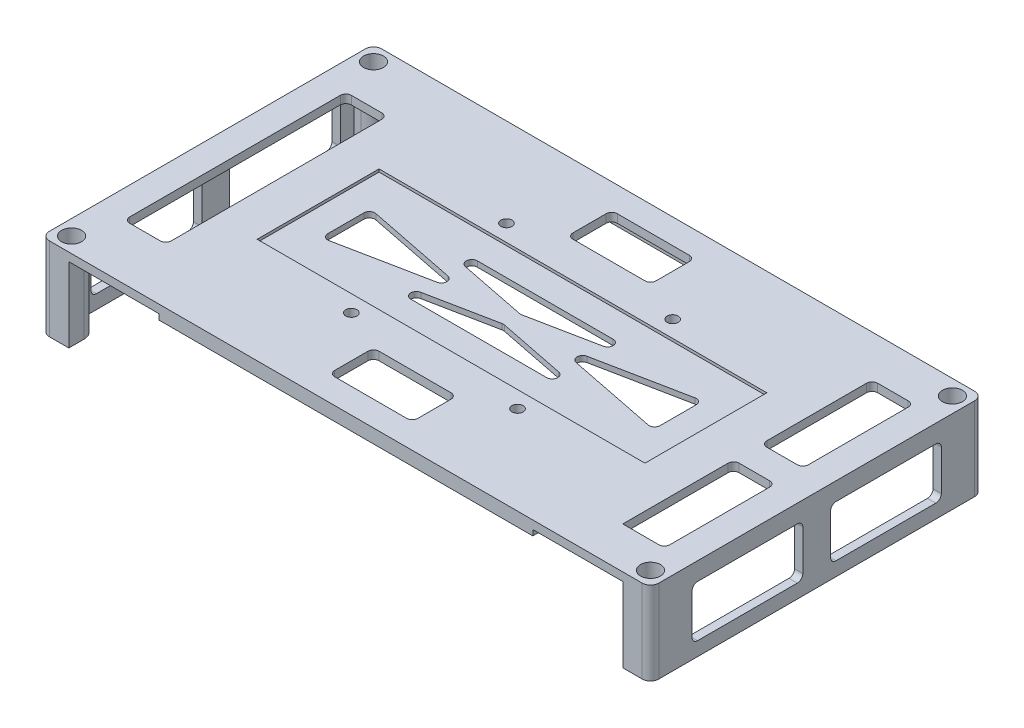
SolidWorks part; units mm, degrees
material "ABS"
ref_plane "前基準面" through (0, 0, 0) normal (0, 0, 1) x (1, 0, 0)
ref_plane "上基準面" through (0, 0, 0) normal (0, 1, 0) x (1, 0, 0)
ref_plane "右基準面" through (0, 0, 0) normal (1, 0, 0) x (0, 0, -1)
sketch "草圖8" plane through (0, 0, 0) normal (0, 1, 0) x (1, 0, 0)
  line L1 (-110, 60) -> (110, 60)
  line L2 (-110, 60) -> (-110, -60)
  line L3 (-110, -60) -> (110, -60)
  line L4 (110, 60) -> (110, -60)
extrude "填料-伸長6" add sketch "草圖8" along normal blind 3
sketch "草圖10" plane through (0, 0, 0) normal (0, -1, 0) x (1, 0, 0)
  line L1 (-110, 60) -> (-100, 60)
  line L2 (-110, 60) -> (-110, -60)
  line L3 (-110, -60) -> (-100, -60)
  line L4 (-100, 60) -> (-100, -60)
  line L5 (0, 0) -> (0, 67.9588) construction
  line L6 (0, 0) -> (59.8785, 0) construction
  line L7 (110, -60) -> (100, -60)
  line L8 (100, 60) -> (100, -60)
  line L9 (110, 60) -> (100, 60)
  line L10 (110, 60) -> (110, -60)
  dimension "D2" = 10
extrude "填料-伸長7" add sketch "草圖10" along normal blind 27
sketch "草圖9" plane through (0, 0, 0) normal (0, 1, 0) x (1, 0, 0)
  line L0 (-1000, 0) -> (49000, 0) construction
  line L1 (0, -994.7968) -> (0, 49005.2032) construction
  line L2 (110, 60) -> (-110, 60) construction
  line L4 (110, -60) -> (110, 60) construction
  circle A0 centre (104.5, 54.5) radius 2.05
  circle A1 centre (-104.5, 54.5) radius 2.05
  circle A2 centre (-104.5, -54.5) radius 2.05
  circle A3 centre (104.5, -54.5) radius 2.05
  circle A6 centre (30, 28) radius 2
  circle A7 centre (-30, 28) radius 2
  circle A8 centre (30, -28) radius 2
  circle A9 centre (-30, -28) radius 2
  dimension "D1" = 4.1
  dimension "D5" = 4
  dimension "D2" = 5.5
  dimension "D3" = 5.5
  dimension "D6" = 30
  dimension "D7" = 28
extrude "除料-伸長1" cut sketch "草圖9" against normal through all and the other way through all contours A1 | A2 | A0 | A3
sketch "草圖11" plane through (0, 3, 0) normal (0, 1, 0) x (1, 0, 0)
  line L0 (0.0013, 21.2615) -> (0.0013, 0) construction
  line L1 (0.0013, 0) -> (-26.9987, 0) construction
  line L2 (110, -60) -> (110, 60) construction
  line L3 (110, 60) -> (-110, 60) construction
  circle A0 centre (-104.4974, 54.5) radius 3.6
  circle A1 centre (-104.4974, -54.5) radius 3.6
  circle A2 centre (104.5, -54.5) radius 3.6
  circle A3 centre (104.5, 54.5) radius 3.6
  dimension "D1" = 7.2
  dimension "D2" = 5.5
  dimension "D4" = 5.5
extrude "除料-伸長2" cut sketch "草圖11" against normal blind 25 contours A1 | A0 | A3 | A2
sketch "草圖13" plane through (0, 0, 0) normal (1, 0, 0) x (0, 0, -1)
  line L0 (0, 0) -> (0, -20.0336) construction
  line L2 (-45, -3.5) -> (-5, -3.5)
  line L3 (-45, -3.5) -> (-45, -22)
  line L4 (-45, -22) -> (-5, -22)
  line L5 (-5, -3.5) -> (-5, -22)
  line L6 (60, -27) -> (-60, -27) construction
  line L8 (45, -3.5) -> (45, -22)
  line L9 (5, -3.5) -> (5, -22)
  line L10 (45, -22) -> (5, -22)
  line L11 (45, -3.5) -> (5, -3.5)
  line L12 (-60, 3) -> (-60, -27) construction
  dimension "D1" = 18.5
  dimension "D2" = 5
  dimension "D3" = 15
  dimension "D4" = 10
extrude "除料-伸長4" cut sketch "草圖13" against normal through all both and the other way through all
sketch "草圖14" plane through (0, 3, 0) normal (0, 1, 0) x (1, 0, 0)
  line L0 (0, 0) -> (-46.215, 0) construction
  line L1 (0, 0) -> (0, 32.6806) construction
  line L3 (-70, -22) -> (70, -22)
  line L4 (-70, -22) -> (-70, 22)
  line L5 (-70, 22) -> (70, 22)
  line L6 (70, -22) -> (70, 22)
  line L7 (-70, -22) -> (70, 22) construction
  line L8 (-70, 22) -> (70, -22) construction
  dimension "D1" = 140
  dimension "D2" = 44
extrude "除料-伸長7" cut sketch "草圖14" against normal blind 1
sketch "草圖15" plane through (0, 3, 0) normal (0, 1, 0) x (1, 0, 0)
  line L0 (0, 0) -> (27.6246, 0) construction
  line L1 (-100, 40) -> (-85, 40)
  line L2 (-100, 40) -> (-100, -40)
  line L3 (-100, -40) -> (-85, -40)
  line L4 (-85, 40) -> (-85, -40)
  line L5 (0, 0) -> (0, 35.214) construction
  line L6 (100, 5) -> (85, 5)
  line L7 (85, 45) -> (85, 5)
  line L8 (100, 45) -> (85, 45)
  line L9 (100, 45) -> (100, 5)
  line L10 (70, 22) -> (-70, 22) construction
  line L11 (-44.7029, -12) -> (44.7029, -12)
  line L12 (-60, -8.9406) -> (-60, 8.9406)
  line L13 (-44.7029, 12) -> (44.7029, 12)
  line L14 (60, -8.9406) -> (60, 8.9406)
  line L15 (-15, -35) -> (15, -35)
  line L16 (0, -3.0594) -> (44.7029, -12)
  line L17 (-70, 22) -> (-70, -22) construction
  line L18 (-60, 8.9406) -> (-15.2971, 0)
  line L19 (-44.7029, -12) -> (0, -3.0594)
  line L20 (-44.7029, 12) -> (0, 3.0594)
  line L21 (-60, -8.9406) -> (-15.2971, 0)
  line L22 (-15, 51) -> (15, 51)
  line L23 (-15, 51) -> (-15, 35)
  line L24 (-15, 35) -> (15, 35)
  line L25 (15, 51) -> (15, 35)
  line L26 (15, -51) -> (15, -35)
  line L27 (-15, -51) -> (15, -51)
  line L28 (15.2971, 0) -> (60, -8.9406)
  line L29 (0, 3.0594) -> (44.7029, 12)
  line L30 (15.2971, 0) -> (60, 8.9406)
  line L31 (-15, -51) -> (-15, -35)
  line L32 (100, -45) -> (100, -5)
  line L33 (100, -45) -> (85, -45)
  line L34 (85, -45) -> (85, -5)
  line L35 (100, -5) -> (85, -5)
  line L36 (110, 60) -> (-110, 60) construction
  dimension "D1" = 40
  dimension "D2" = 85
  dimension "D3" = 15
  dimension "D4" = 10
  dimension "D5" = 10
  dimension "D6" = 30
  dimension "D7" = 16
  dimension "D8" = 35
  dimension "D9" = 85
  dimension "D10" = 80
  dimension "D11" = 15
extrude "除料-伸長8" cut sketch "草圖15" against normal through all
extrude "除料-伸長9" cut sketch "草圖9<5>" along normal through all contours A7 | A6 | A9 | A8
sketch "草圖9<5>" plane through (0, 0, 0) normal (0, 1, 0) x (1, 0, 0) same geometry as "草圖9"
sketch "草圖19" plane through (0, -27, 0) normal (0, -1, 0) x (1, 0, 0)
  line L5 (0, -57.1205) -> (0, 57.1205) construction
  line L6 (0, 0) -> (-76.5655, 0) construction
  line L12 (-100, 54.5) -> (-100, -54.5)
  line L15 (-110, 60) -> (-110, -60) construction
  line L16 (-104.5, 50) -> (-107, 50)
  line L18 (-104.5, -50) -> (-107, -50)
  line L19 (-107, 50) -> (-107, -50)
  line L20 (100, 54.5) -> (100, -54.5)
  line L21 (104.5, -50) -> (107, -50)
  line L22 (107, 50) -> (107, -50)
  line L23 (104.5, 50) -> (107, 50)
  arc A0 (-104.5, 50) -> (-100, 54.5) centre (-104.5, 54.5) ccw
  arc A1 (-104.5, -50) -> (-100, -54.5) centre (-104.5, -54.5) cw
  arc A4 (104.5, 50) -> (100, 54.5) centre (104.5, 54.5) cw
  arc A5 (104.5, -50) -> (100, -54.5) centre (104.5, -54.5) ccw
  point P10 (0, 0)
  dimension "D2" = 9
  dimension "D1" = 3
extrude "除料-伸長13" cut sketch "草圖19" against normal blind 27
sketch "草圖20" plane through (0, 0, 0) normal (0, -1, 0) x (1, 0, 0)
  line L0 (0, 0) -> (0, 103.9697) construction
  line L1 (0, 0) -> (143.2508, 0) construction
  line L2 (-100, 60) -> (100, 60) construction
  line L3 (-67.5, 60) -> (67.5, 60)
  line L4 (-67.5, 60) -> (-67.5, 52)
  line L5 (-67.5, 52) -> (67.5, 52)
  line L6 (67.5, 60) -> (67.5, 52)
  line L7 (-67.5, -52) -> (67.5, -52)
  line L8 (67.5, -60) -> (67.5, -52)
  line L9 (-67.5, -60) -> (67.5, -60)
  line L10 (-67.5, -60) -> (-67.5, -52)
  line L12 (-59, 32.5) -> (-39, 32.5)
  line L13 (-59, 32.5) -> (-59, 25)
  line L14 (-59, 25) -> (-54, 25)
  line L15 (-39, 32.5) -> (-39, 29.5)
  line L28 (-85, 40) -> (-85, -40) construction
  line L31 (-54, 25) -> (-54, 29.5)
  line L32 (-54, 29.5) -> (-39, 29.5)
  line L33 (54, 29.5) -> (39, 29.5)
  line L34 (54, 25) -> (54, 29.5)
  line L35 (39, 32.5) -> (39, 29.5)
  line L36 (59, 25) -> (54, 25)
  line L37 (59, 32.5) -> (59, 25)
  line L38 (59, 32.5) -> (39, 32.5)
  line L39 (59, -32.5) -> (39, -32.5)
  line L40 (59, -32.5) -> (59, -25)
  line L41 (59, -25) -> (54, -25)
  line L42 (39, -32.5) -> (39, -29.5)
  line L43 (54, -25) -> (54, -29.5)
  line L44 (54, -29.5) -> (39, -29.5)
  line L45 (-54, -29.5) -> (-39, -29.5)
  line L46 (-54, -25) -> (-54, -29.5)
  line L47 (-39, -32.5) -> (-39, -29.5)
  line L48 (-59, -25) -> (-54, -25)
  line L49 (-59, -32.5) -> (-59, -25)
  line L50 (-59, -32.5) -> (-39, -32.5)
  dimension "D1" = 135
  dimension "D2" = 8
  dimension "D3" = 20
  dimension "D4" = 7.5
  dimension "D5" = 26
  dimension "D6" = 25
  dimension "D7" = 3
  dimension "D8" = 5
extrude "填料-伸長8" add sketch "草圖20" along normal blind 2
fillet "圓角1" radius 3 4 edges at (-110, -12, 60) (-110, -12, -60) (110, -12, -60) (110, -12, 60)
fillet "圓角2" radius 2 49 edges at (-107, 0, 0) (107, 0, 0) (108.5, -3.5, -5) (108.5, -3.5, 45) (108.5, -22, 45) (108.5, -22, -5) (108.5, -3.5, -45) (108.5, -3.5, 5) (108.5, -22, 5) (108.5, -22, -45) (-108.5, -22, -45) (-108.5, -22, 5) (-108.5, -3.5, -45) (-108.5, -3.5, 5) (-108.5, -22, 45) (-108.5, -3.5, 45) (-108.5, -3.5, -5) (-108.5, -22, -5) (60, 1, -8.9406) (44.7029, 1, -12) (-44.7029, 1, -12) (0, 1, 3.0594) (-44.7029, 1, 12) (44.7029, 1, 12) (-15.2971, 1, 0) (0, 1, -3.0594) (60, 1, 8.9406) (100, 1.5, -5) (15, 1.5, -35) (100, 1.5, 45) (15, 1.5, 51) (-85, 1.5, 40) (-15, 1.5, 51) (85, 1.5, -5) (15.2971, 1, 0) (-100, 1.5, 40) (-15, 1.5, -35) (-60, 1, 8.9406) (-60, 1, -8.9406) (15, 1.5, 35) (-15, 1.5, 35) (85, 1.5, 5) (85, 1.5, -45) (100, 1.5, 5) (100, 1.5, -45) (15, 1.5, -51) (-15, 1.5, -51) (-85, 1.5, -40) (-100, 1.5, -40)
